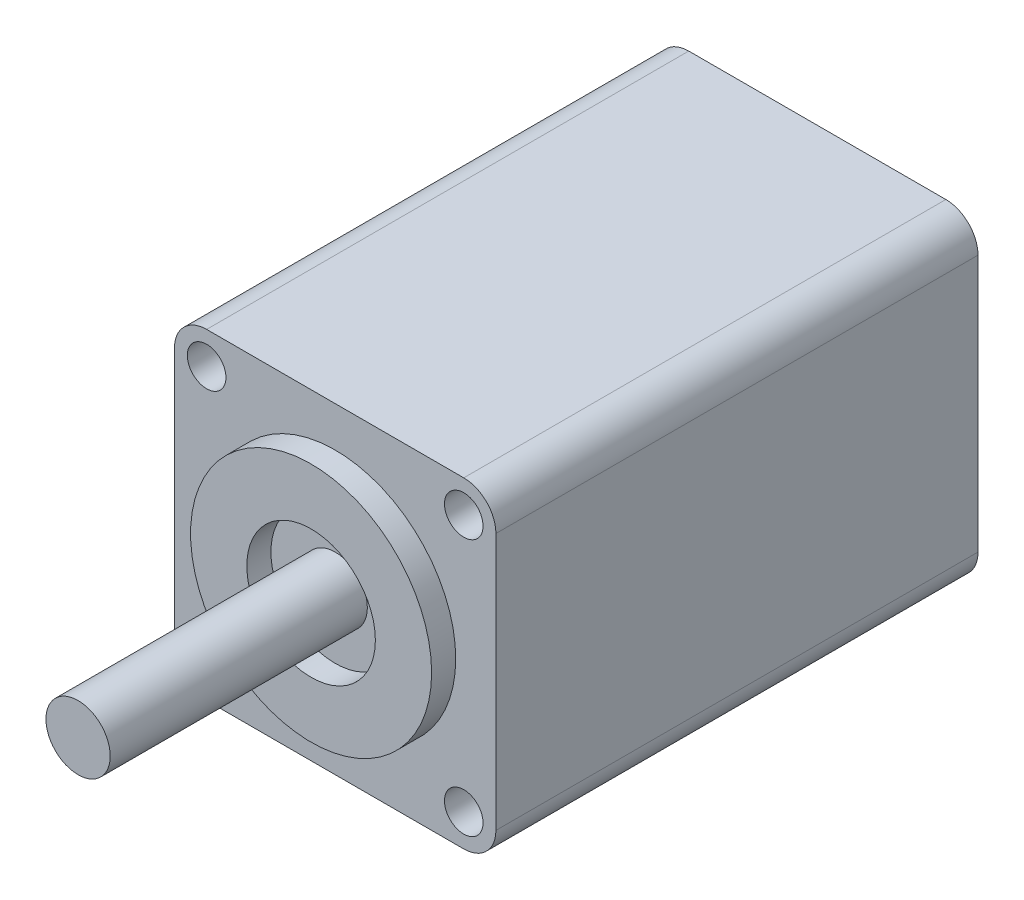
SolidWorks part; units mm, degrees
ref_plane "Front Plane" through (0, 0, 0) normal (0, 0, 1) x (1, 0, 0)
ref_plane "Top Plane" through (0, 0, 0) normal (0, 1, 0) x (1, 0, 0)
ref_plane "Right Plane" through (0, 0, 0) normal (1, 0, 0) x (0, 0, -1)
sketch "Sketch1" plane through (0, 0, 0) normal (0, 0, 1) x (1, 0, 0)
  line L1 (-8, -10) -> (8, -10)
  line L2 (-10, -8) -> (-10, 8)
  line L3 (-8, 10) -> (8, 10)
  line L4 (10, -8) -> (10, 8)
  line L5 (-10, -10) -> (10, 10) construction
  line L6 (-10, 10) -> (10, -10) construction
  arc A0 (-10, -8) -> (-8, -10) centre (-8, -8) ccw
  arc A1 (8, -10) -> (10, -8) centre (8, -8) ccw
  arc A2 (8, 10) -> (10, 8) centre (8, 8) cw
  arc A3 (-8, 10) -> (-10, 8) centre (-8, 8) ccw
  point P0 (0, 0)
  dimension "D1" = 2
  dimension "D2" = 20
extrude "Boss-Extrude1" add sketch "Sketch1" against normal blind 30
sketch "Sketch3" plane through (0, 0, 0) normal (0, 0, 1) x (1, 0, 0)
  circle A0 centre (0, 0) radius 7.5
  circle A1 centre (0, 0) radius 4
  dimension "D1" = 15
  dimension "D2" = 8
extrude "Boss-Extrude2" add sketch "Sketch3" along normal blind 1.5
sketch "Sketch4" plane through (0, 0, 0) normal (0, 0, 1) x (1, 0, 0)
  circle A0 centre (0, 0) radius 2
  dimension "D1" = 4
extrude "Boss-Extrude3" add sketch "Sketch4" along normal blind 16
hole_wizard "M2 Clearance Hole1" positions "Sketch6" profile "Sketch5" hole size "M2" standard "Ansi Metric"
sketch "Sketch6" plane through (0, 0, 0) normal (0, 0, 1) x (1, 0, 0)
  line L0 (0, 8.4636) -> (0, -8.5685) construction
  line L2 (-8.6512, 0) -> (8.8383, 0) construction
  point P0 (-8, 8)
  point P1 (8, 8)
  point P3 (8, -8)
  point P5 (-8, -8)
  dimension "D1" = 16
  dimension "D2" = 16
sketch "Sketch5" plane through (-8, 8, 0) normal (1, 0, 0) x (0, -1, 0)
  line L0 (0, 0) -> (0, 4.221)
  line L1 (0, 4.221) -> (1.2, 3.5)
  line L2 (1.2, 3.5) -> (1.2, 0)
  line L5 (1.2, 0) -> (0, 0)
  line L10 (0, 4.221) -> (-1.2, 3.5) construction
  line L11 (0, -6.35) -> (0, 107.95) construction
  dimension "Hole Dia." = 2.4
  dimension "Hole Depth" = 3.5
  dimension "Drill Angle" = 118
ref_axis "Motor Shaft Axis" through (0, 0, 16) along (0, 0, -1)
